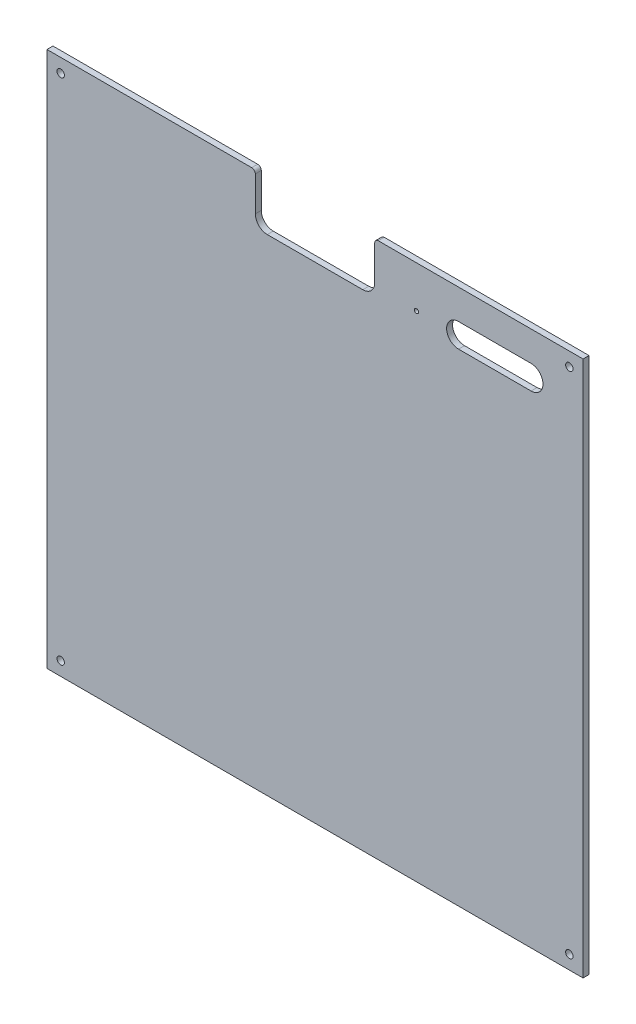
SolidWorks part; units mm, degrees
material "ABS PC"
ref_plane "Piano frontale" through (0, 0, 0) normal (0, 0, 1) x (1, 0, 0)
ref_plane "Piano superiore" through (0, 0, 0) normal (0, 1, 0) x (1, 0, 0)
ref_plane "Piano destro" through (0, 0, 0) normal (1, 0, 0) x (0, 0, -1)
sketch "Schizzo1" plane through (0, 0, 0) normal (0, 0, 1) x (1, 0, 0)
  line L0 (0, 0) -> (0, 449)
  line L1 (0, 449) -> (171.5, 449)
  line L2 (449, 449) -> (449, 0)
  line L3 (449, 0) -> (0, 0)
  line L4 (174.5, 446) -> (174.5, 417)
  line L5 (184.5, 407) -> (264.5, 407)
  line L6 (274.5, 417) -> (274.5, 446)
  line L7 (277.5, 449) -> (449, 449)
  line L8 (154.5, 414) -> (294.5, 414) construction
  line L9 (224.5, 379) -> (224.5, 419) construction
  line L10 (344.7159, 414) -> (405.4404, 414) construction
  line L11 (344.7159, 424) -> (405.4404, 424)
  line L12 (344.7159, 404) -> (405.4404, 404)
  line L13 (0, 224.5) -> (449, 224.5) construction
  line L23 (73.9219, 399) -> (73.9219, 449) construction
  line L24 (174.5, 431.5) -> (314.5, 431.5) construction
  arc A0 (174.5, 417) -> (184.5, 407) centre (184.5, 417) ccw
  arc A1 (274.5, 417) -> (264.5, 407) centre (264.5, 417) cw
  circle A2 centre (11.5, 11.5) radius 3.1
  circle A3 centre (437.5, 11.5) radius 3.1
  circle A4 centre (437.5, 437.5) radius 3.1
  circle A5 centre (11.5, 437.5) radius 3.1
  circle A6 centre (309.5, 414) radius 1.75
  arc A7 (277.5, 449) -> (274.5, 446) centre (277.5, 446) ccw
  arc A8 (344.7159, 424) -> (344.7159, 404) centre (344.7159, 414) ccw
  arc A9 (405.4404, 404) -> (405.4404, 424) centre (405.4404, 414) ccw
  arc A10 (174.5, 446) -> (171.5, 449) centre (171.5, 446) ccw
  point P11 (174.5, 407)
  point P14 (274.5, 407)
  point P33 (375.0781, 414)
  point P44 (174.5, 449)
  dimension "D5" = 10
  dimension "D6" = 11.5
  dimension "D7" = 11.5
  dimension "D8" = 6.2
  dimension "D9" = 3.5
  dimension "D10" = 35
  dimension "D12" = 3
  dimension "D1" = 449
  dimension "D2" = 449
  dimension "D3" = 100
  dimension "D4" = 42
  dimension "D11" = 20
  dimension "D21" = 35
extrude "Estrusione-Estrusione1" add sketch "Schizzo1" along normal blind 5
